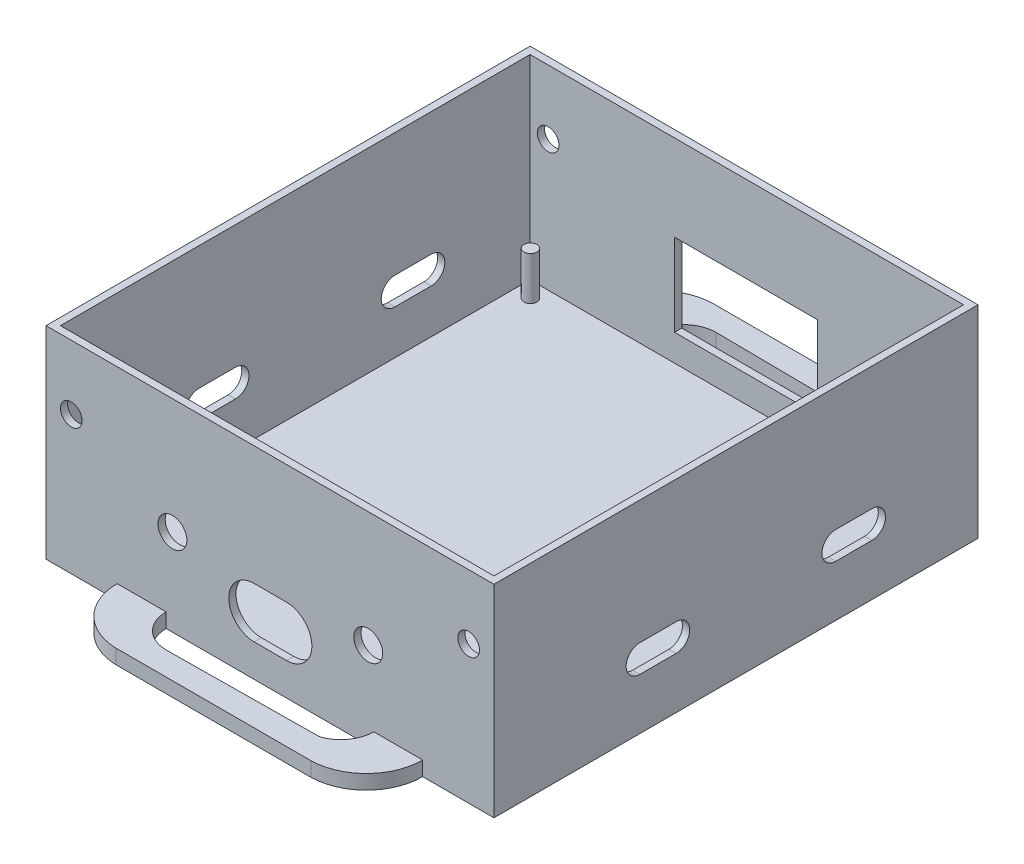
SolidWorks part; units mm, degrees
ref_plane "Спереди" through (0, 0, 0) normal (0, 0, 1) x (1, 0, 0)
ref_plane "Сверху" through (0, 0, 0) normal (0, 1, 0) x (1, 0, 0)
ref_plane "Справа" through (0, 0, 0) normal (1, 0, 0) x (0, 0, -1)
sketch "Эскиз1" plane through (0, 0, 0) normal (0, 1, 0) x (1, 0, 0)
  line L0 (31, -33.5) -> (-31, -33.5)
  line L1 (31, -33.5) -> (31, 33.5)
  line L2 (-31, -33.5) -> (-31, 33.5)
  line L3 (31, 33.5) -> (-31, 33.5)
  line L4 (31, -33.5) -> (-31, 33.5) construction
  line L5 (-31, -33.5) -> (31, 33.5) construction
  point P1 (0, 0)
  dimension "D1" = 62
  dimension "D2" = 67
extrude "Бобышка-Вытянуть1" add sketch "Эскиз1" along normal blind 1
sketch "Эскиз3" plane through (0, 1, 0) normal (0, 1, 0) x (1, 0, 0)
  line L0 (-27.75, 30.3) -> (27.75, 30.3) construction
  line L1 (-27.75, 30.3) -> (-27.75, -30.3) construction
  line L2 (27.75, 30.3) -> (27.75, -30.3) construction
  line L3 (-27.75, -30.3) -> (27.75, -30.3) construction
  line L4 (-27.75, 30.3) -> (27.75, -30.3) construction
  line L5 (27.75, 30.3) -> (-27.75, -30.3) construction
  line L6 (0, 0) -> (15.2708, 0) construction
  line L7 (0, 0) -> (0, -20.8266) construction
  circle A0 centre (27.75, -30.3) radius 0.9
  circle A1 centre (27.75, 30.3) radius 0.9
  circle A2 centre (-27.75, -30.3) radius 0.9
  circle A3 centre (-27.75, 30.3) radius 0.9
  point P1 (0, 0)
  dimension "D3" = 1.8
  dimension "D1" = 55.5
  dimension "D2" = 60.6
extrude "Бобышка-Вытянуть2" add sketch "Эскиз3" along normal blind 6
sketch "Эскиз5" plane through (0, 1, 0) normal (0, 1, 0) x (1, 0, 0)
  line L0 (30, 32.5) -> (30, -32.5)
  line L1 (30, 32.5) -> (-30, 32.5)
  line L2 (30, -32.5) -> (-30, -32.5)
  line L3 (-30, 32.5) -> (-30, -32.5)
  line L4 (30, 32.5) -> (-30, -32.5) construction
  line L5 (30, -32.5) -> (-30, 32.5) construction
  line L6 (31, -33.5) -> (31, 33.5) construction
  line L7 (31, 33.5) -> (-31, 33.5) construction
  line L8 (-31, 33.5) -> (-31, -33.5) construction
  line L9 (-31, -33.5) -> (31, -33.5) construction
  line L10 (31, -33.5) -> (31, 33.5)
  line L11 (31, 33.5) -> (-31, 33.5)
  line L12 (-31, 33.5) -> (-31, -33.5)
  line L13 (-31, -33.5) -> (31, -33.5)
  point P1 (0, 0)
  dimension "D1" = 65
  dimension "D2" = 60
extrude "Бобышка-Вытянуть3" add sketch "Эскиз5" along normal blind 27
sketch "Эскиз6" plane through (0, 0, -33.5) normal (0, 0, -1) x (-1, 0, 0)
  line L0 (-9.8, 23.2886) -> (-9.8, -25.1641) construction
  line L1 (11.6632, 4.7) -> (-9.8, 4.7) construction
  line L2 (-31, 0) -> (31, 0) construction
  line L3 (-31, 28) -> (-31, 0) construction
  line L4 (-10.2124, 16.1) -> (13.619, 16.1) construction
  line L5 (10, 18.7059) -> (10, -1.9863) construction
  line L6 (31, 28) -> (31, 0) construction
  line L7 (10, 4.7) -> (10, 16.1)
  line L8 (10, 16.1) -> (-9.8, 16.1)
  line L9 (-9.8, 16.1) -> (-9.8, 4.7)
  line L10 (-9.8, 4.7) -> (10, 4.7)
  dimension "D1" = 4.7
  dimension "D2" = 21.2
  dimension "D3" = 11.4
  dimension "D4" = 21
extrude "Вырез-Вытянуть1" cut sketch "Эскиз6" against normal blind 2
sketch "Эскиз7" plane through (31, 0, 0) normal (1, 0, 0) x (0, 0, -1)
  line L4 (-33.5, 0) -> (33.5, 0)
  line L5 (33.5, 0) -> (33.5, 28)
  line L6 (33.5, 28) -> (-33.5, 28)
  line L7 (-33.5, 28) -> (-33.5, 0)
  line L8 (-33.5, 0) -> (33.5, 0)
  line L9 (33.5, 0) -> (33.5, 28)
  line L10 (33.5, 28) -> (-33.5, 28)
  line L11 (-33.5, 28) -> (-33.5, 0)
  line L14 (-10.8, 9) -> (-10.8, 22.4208) construction
  line L15 (16.3, 9) -> (16.3, 24.1765) construction
  line L16 (-13.3, 9) -> (-8.3, 9) construction
  line L17 (-13.3, 10.9) -> (-8.3, 10.9)
  line L18 (-13.3, 7.1) -> (-8.3, 7.1)
  line L19 (13.8, 9) -> (18.8, 9) construction
  line L20 (13.8, 10.9) -> (18.8, 10.9)
  line L21 (13.8, 7.1) -> (18.8, 7.1)
  arc A0 (-13.3, 10.9) -> (-13.3, 7.1) centre (-13.3, 9) ccw
  arc A1 (-8.3, 7.1) -> (-8.3, 10.9) centre (-8.3, 9) ccw
  arc A2 (13.8, 10.9) -> (13.8, 7.1) centre (13.8, 9) ccw
  arc A3 (18.8, 7.1) -> (18.8, 10.9) centre (18.8, 9) ccw
  point P16 (-10.8, 9)
  point P23 (16.3, 9)
  dimension "D4" = 1.9
  dimension "D6" = 1.9
  dimension "D2" = 9
  dimension "D5" = 5
  dimension "D7" = 5
  dimension "D1" = 0
extrude "Вырез-Вытянуть2" cut sketch "Эскиз7" against normal through all both and the other way through all contours L18 A1 L17 A0 | L21 A3 L20 A2
sketch "Эскиз8" plane through (0, 0, 33.5) normal (0, 0, 1) x (1, 0, 0)
  line L0 (-26.85, 7) -> (-28.65, 7) construction
  line L1 (-26.85, 7) -> (-28.65, 7)
  line L2 (-26.85, 7) -> (-28.65, 7)
  line L3 (-27.75, 7) -> (0.05, 7) construction
  line L4 (-31, 0) -> (31, 0)
  line L5 (31, 0) -> (31, 28)
  line L6 (31, 28) -> (-31, 28)
  line L7 (-31, 28) -> (-31, 0)
  line L8 (-31, 0) -> (31, 0)
  line L9 (31, 0) -> (31, 28)
  line L10 (31, 28) -> (-31, 28)
  line L11 (-31, 28) -> (-31, 0)
  line L12 (0.05, 7) -> (0.05, 6) construction
  line L13 (0.05, 7) -> (0.05, 8) construction
  line L14 (2.3, 8) -> (-2.2, 8) construction
  line L15 (2.3, 4.5) -> (-2.2, 4.5)
  line L16 (2.3, 11.5) -> (-2.2, 11.5)
  arc A0 (2.3, 4.5) -> (2.3, 11.5) centre (2.3, 8) ccw
  arc A1 (-2.2, 11.5) -> (-2.2, 4.5) centre (-2.2, 8) ccw
  circle A2 centre (-13.5, 12) radius 2
  circle A3 centre (13.6, 12) radius 2
  point P12 (0.05, 8)
  dimension "D6" = 4.5
  dimension "D7" = 4
  dimension "D2" = 27.8
  dimension "D3" = 1
  dimension "D4" = 1
  dimension "D5" = 7
  dimension "D8" = 17.5
  dimension "D9" = 12
  dimension "D1" = 0
extrude "Вырез-Вытянуть3" cut sketch "Эскиз8" against normal blind 2 contours L16 A1 L15 A0 region at (0.05, 8, 33.5)
extrude "Вырез-Вытянуть4" cut sketch "Эскиз8<3>" against normal blind 10 contours A2 | A3 region at (-13.5, 12, 33.5) region at (13.6, 12, 33.5)
sketch "Эскиз8<3>" plane through (0, 0, 33.5) normal (0, 0, 1) x (1, 0, 0) same geometry as "Эскиз8"
sketch "Эскиз9" plane through (0, 0, 33.5) normal (0, 0, 1) x (1, 0, 0)
  line L0 (-27.5, 18.332) -> (-27.5, 31.336) construction
  line L1 (-31, 28) -> (-31, 0) construction
  line L2 (-29.0851, 19.1) -> (-19.5274, 19.1) construction
  line L3 (-31, 28) -> (31, 28) construction
  line L4 (0, 0) -> (0, 20.0042) construction
  line L5 (-31, 0) -> (31, 0) construction
  circle A0 centre (-27.5, 19.1) radius 1.5
  circle A1 centre (27.5, 19.1) radius 1.5
  dimension "D3" = 3
  dimension "D1" = 3.5
  dimension "D2" = 8.9
extrude "Вырез-Вытянуть5" cut sketch "Эскиз9" against normal through all
sketch "Эскиз10" plane through (0, 0, 0) normal (0, -1, 0) x (1, 0, 0)
  line L0 (0, 0) -> (0, -28.9383) construction
  line L1 (14.3709, -33.5) -> (21.1432, -33.5)
  line L2 (31, -33.5) -> (-31, -33.5) construction
  line L4 (-13.5, -41.3115) -> (13.5, -41.3115)
  line L6 (11.1897, -37.8478) -> (-9.8092, -38.0617)
  line L8 (-21.1432, -33.5) -> (-14.3709, -33.5)
  line L9 (0, -33.5) -> (0, -45.0064) construction
  line L12 (-31, -33.5) -> (-31, 33.5) construction
  line L13 (31, 33.5) -> (31, -33.5) construction
  line L14 (0, 0) -> (25.9542, 0) construction
  line L15 (-21.1432, 33.5) -> (-14.3921, 33.5)
  line L16 (14.3709, 33.5) -> (21.1432, 33.5)
  line L17 (-13.5, 41.3115) -> (13.5, 41.3115)
  line L18 (11.1897, 37.8478) -> (-9.8092, 38.0617)
  line L19 (-14.3921, 33.5) -> (-14.3709, 33.5)
  arc A0 (-21.1432, -33.5) -> (-13.5, -41.3115) centre (-13.3299, -33.5) ccw
  arc A1 (13.5, -41.3115) -> (21.1432, -33.5) centre (13.3299, -33.5) ccw
  arc A2 (11.1897, -37.8478) -> (14.3709, -33.5) centre (9.8092, -33.5) ccw
  arc A3 (-14.3709, -33.5) -> (-9.8092, -38.0617) centre (-9.8092, -33.5) ccw
  arc A4 (13.5, 41.3115) -> (21.1432, 33.5) centre (13.3299, 33.5) cw
  arc A5 (-21.1432, 33.5) -> (-13.5, 41.3115) centre (-13.3299, 33.5) cw
  arc A6 (11.1897, 37.8478) -> (14.3709, 33.5) centre (9.8092, 33.5) cw
  arc A7 (-14.3709, 33.5) -> (-9.8092, 38.0617) centre (-9.8092, 33.5) cw
  point P7 (0, -33.5)
  point P13 (0, -33.5)
  dimension "D1" = 21
  dimension "D2" = 27
  dimension "D3" = 17.5
  dimension "D4" = 17.5
extrude "Бобышка-Вытянуть4" add sketch "Эскиз10" against normal blind 2
